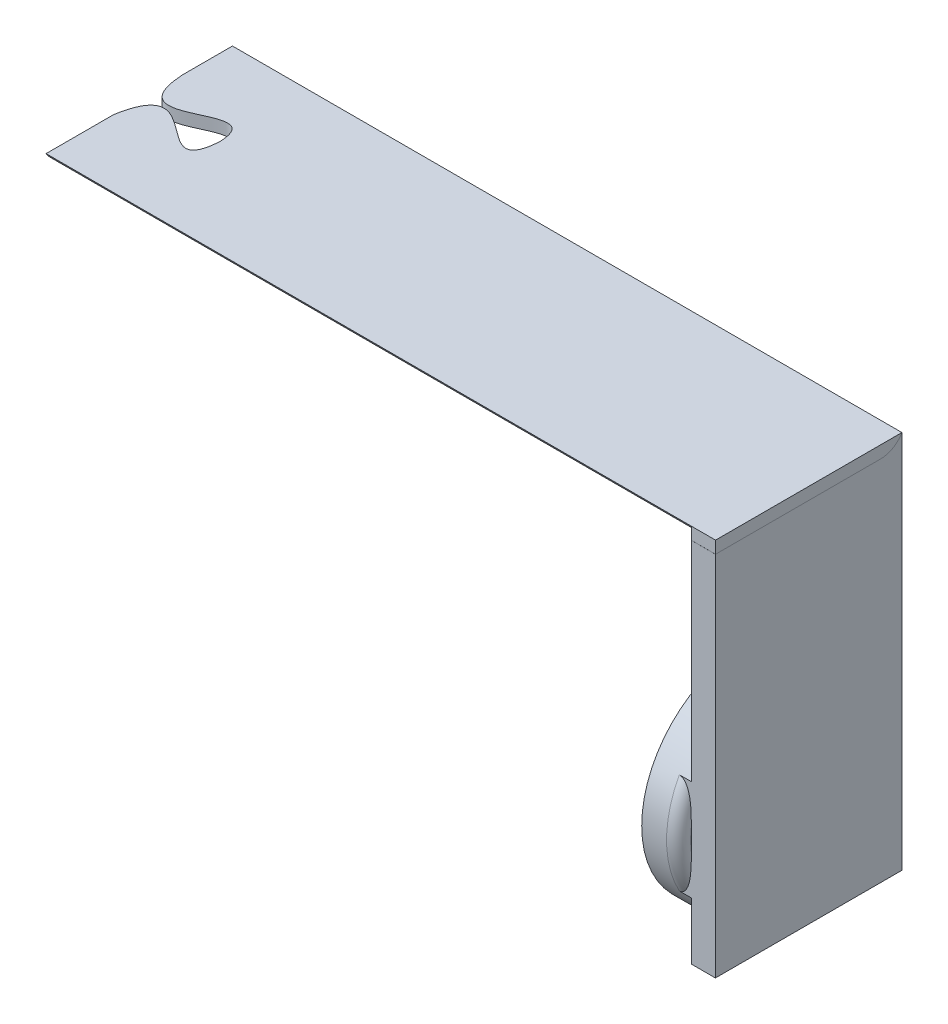
SolidWorks part; units mm, degrees
ref_plane "Front Plane" through (0, 0, 0) normal (0, 0, 1) x (1, 0, 0)
ref_plane "Top Plane" through (0, 0, 0) normal (0, 1, 0) x (1, 0, 0)
ref_plane "Right Plane" through (0, 0, 0) normal (1, 0, 0) x (0, 0, -1)
sketch "Sketch1" plane through (0, 0, 0) normal (0, 1, 0) x (1, 0, 0)
  line L0 (0, 28.2938) -> (0, 38.695)
  line L1 (0, 0) -> (139, 0)
  line L2 (0, 0) -> (0, 14.0452)
  line L3 (0, 38.695) -> (139, 38.695)
  line L4 (139, 0) -> (139, 38.695)
  spline S0 degree 3 poles (0, 28.2938) (1.0033, 11.1588) (15.6582, 32.9988) (15.8766, 19.9366) knots 0 0 0 0 1 1 1 1
  spline S1 degree 3 poles (0, 14.0452) (3.09, 31.623) (14.6825, 5.6776) (15.8766, 19.9366) knots 0 0 0 0 1 1 1 1
extrude "Boss-Extrude1" add sketch "Sketch1" along normal blind 2.54
sketch "Sketch5" plane through (0, 0, 0) normal (0, -1, 0) x (1, 0, 0)
  line L1 (138.9819, -38.6843) -> (133.9819, -38.6843)
  line L2 (138.9819, -38.6843) -> (138.9819, 0.0107)
  line L3 (138.9819, 0.0107) -> (133.9819, 0.0107)
  line L4 (133.9819, -38.6843) -> (133.9819, 0.0107)
extrude "Boss-Extrude2" add sketch "Sketch5" along normal blind 76.2
sketch "Sketch6" plane through (133.9819, 0, 0) normal (-1, 0, 0) x (0, 0, 1)
  circle A0 centre (-19.3475, -53.848) radius 18.6
  circle A1 centre (-19.3475, -53.848) radius 22
extrude "Boss-Extrude5" add sketch "Sketch6" along normal blind 7.6604
fillet "Fillet10" radius 2.5 1 edges at (133.9819, -53.848, -41.3475)
fillet "Fillet11" radius 2.5 1 edges at (133.9819, -53.848, 2.6525)
fillet "Fillet13" radius 5.5709 1 edges at (126.3215, -53.848, -0.7475)
fillet "Fillet15" radius 5.08 1 edges at (69.5, 0, -38.695)
fillet "Fillet16" radius 5.08 1 edges at (66.991, 0, 0)
